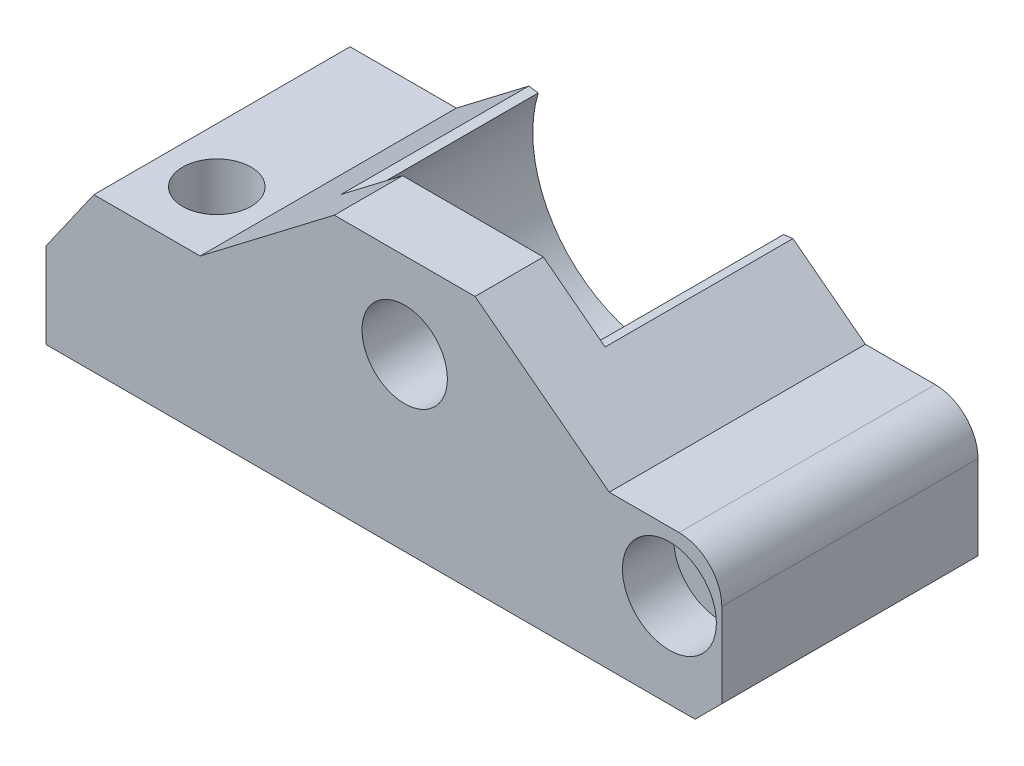
SolidWorks part; units mm, degrees
material "6061-O (SS)"
ref_plane "Piano frontale" through (0, 0, 0) normal (0, 0, 1) x (1, 0, 0)
ref_plane "Piano superiore" through (0, 0, 0) normal (0, 1, 0) x (1, 0, 0)
ref_plane "Piano destro" through (0, 0, 0) normal (1, 0, 0) x (0, 0, -1)
sketch "Schizzo2" plane through (0, 0, 0) normal (0, 0, 1) x (1, 0, 0)
  line L0 (-40, 0) -> (-2, 0)
  line L1 (-40, 0) -> (-40, 9)
  line L2 (-19, 0) -> (-19, 25.5566) construction
  line L3 (-40, 9) -> (-30.9754, 9)
  line L4 (-30.9754, 9) -> (-23.1199, 15)
  line L5 (-23.1199, 15) -> (-14.8801, 15)
  line L6 (-7.0246, 9) -> (-14.8801, 15)
  line L7 (-0.4334, 9) -> (-7.0246, 9)
  line L8 (-0.4334, 1.5666) -> (-2, 0)
  line L11 (-0.4334, 9) -> (-0.4334, 1.5666)
  circle A0 centre (-19, 10) radius 2.5
  circle A1 centre (-3.5, 5.5) radius 1.3432
  point P0 (-40, 0)
  point P1 (2, 0)
  point P10 (-19, 15)
  dimension "D3" = 5
  dimension "D4" = 15
  dimension "D1" = 42
  dimension "D2" = 9
  dimension "D5" = 10
  dimension "D6" = 15.5
  dimension "D7" = 5.5
  dimension "D9" = 4
extrude "Estrusione-Estrusione1" add sketch "Schizzo2" against normal blind 15
sketch "Schizzo3" plane through (0, 0, -15) normal (0, 0, -1) x (-1, 0, 0)
  circle A0 centre (19, 10) radius 7.5
  circle A1 centre (19, 10) radius 2.5 construction
  dimension "D1" = 15
extrude "Taglio-Estrusione1" cut sketch "Schizzo3" against normal blind 11
sketch "Schizzo4" plane through (0, 0, 0) normal (0, 0, 1) x (1, 0, 0)
  circle A0 centre (-3.5, 5.5) radius 2.75
  dimension "D1" = 5.5
extrude "Taglio-Estrusione2" cut sketch "Schizzo4" against normal blind 3
chamfer "Smusso3" distance 1 angle 45 2 edges at (-12.0614, 12.8471, -9.5) (-25.9386, 12.8471, -9.5) first distance on face at (-11.322, 12.2824, -6.3333) first distance on face at (-26.678, 12.2824, -6.3333)
fillet "Raccordo1" radius 2.5 1 edges at (-0.4334, 9, -7.5)
chamfer "Smusso4" distance 4 angle 35 1 edges at (-40, 9, -7.5) first distance on face at (-40, 4.5, -7.5)
sketch "Schizzo5" plane through (0, 0, 0) normal (0, -1, 0) x (1, 0, 0)
  line L0 (0, -4) -> (39.5666, -4) construction
  line L1 (-40, -15) -> (-40, 0) construction
  line L3 (-40, 0) -> (-2, 0) construction
  circle A0 centre (-34, -4) radius 2
  dimension "D3" = 4
  dimension "D1" = 6
  dimension "D2" = 4
extrude "Taglio-Estrusione3" cut sketch "Schizzo5" against normal through all
